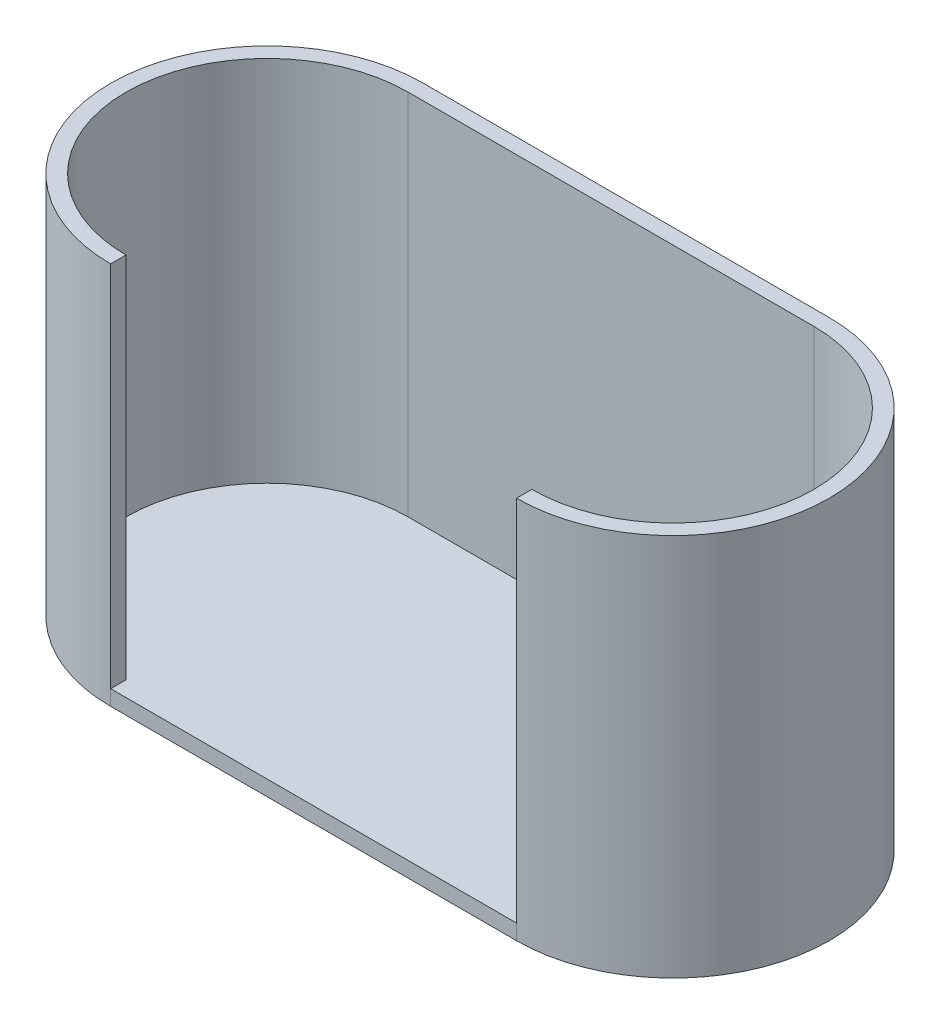
SolidWorks part; units mm, degrees
ref_plane "정면" through (0, 0, 0) normal (0, 0, 1) x (1, 0, 0)
ref_plane "윗면" through (0, 0, 0) normal (0, 1, 0) x (1, 0, 0)
ref_plane "우측면" through (0, 0, 0) normal (1, 0, 0) x (0, 0, -1)
sketch "Sketch1" plane through (0, 0, 0) normal (0, 1, 0) x (1, 0, 0)
  line L0 (-26.4773, 0) -> (26.4773, 0) construction
  line L1 (-26.4773, 20.407) -> (26.4773, 20.407)
  line L2 (-26.4773, -20.407) -> (26.4773, -20.407)
  arc A0 (-26.4773, 20.407) -> (-26.4773, -20.407) centre (-26.4773, 0) ccw
  arc A1 (26.4773, -20.407) -> (26.4773, 20.407) centre (26.4773, 0) ccw
  point P3 (0, 0)
  point P8 (0, 0)
extrude "Boss-Extrude1" add sketch "Sketch1" along normal blind 50
shell "Shell2" thickness 2 removed face at (0, 25, 20.407) removed face at (0, 50, 0)
